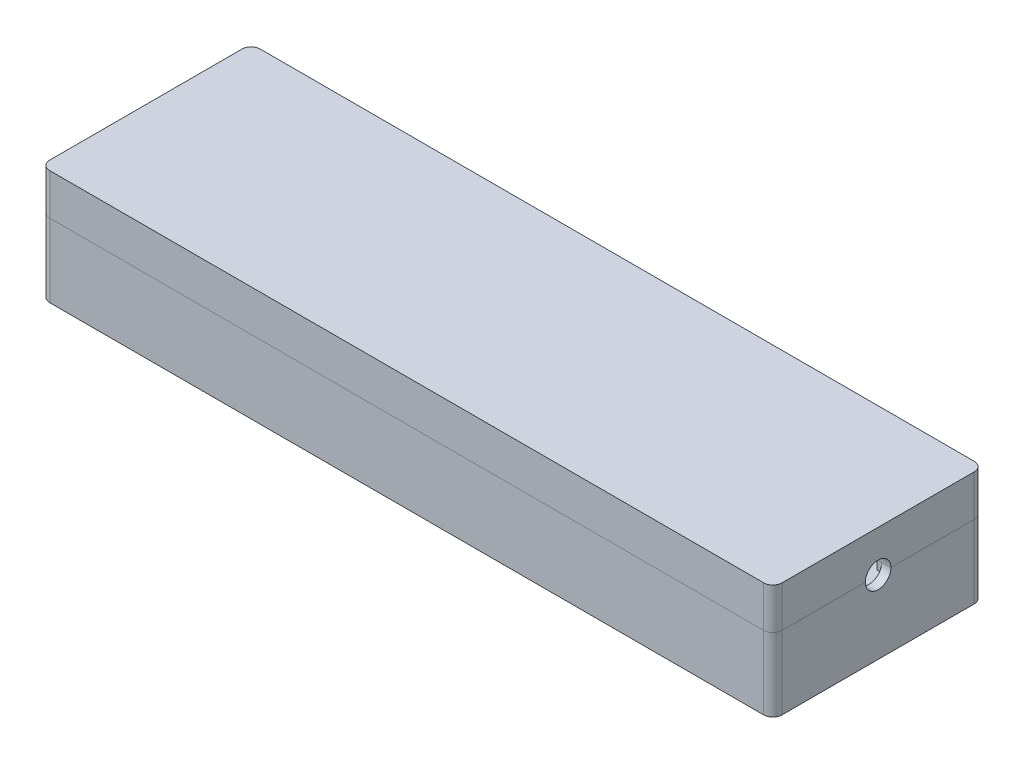
SolidWorks part; units mm, degrees
ref_plane "Front Plane" through (0, 0, 0) normal (0, 0, 1) x (1, 0, 0)
ref_plane "Top Plane" through (0, 0, 0) normal (0, 1, 0) x (1, 0, 0)
ref_plane "Right Plane" through (0, 0, 0) normal (1, 0, 0) x (0, 0, -1)
sketch "Sketch1" plane through (0, 0, 0) normal (0, 1, 0) x (1, 0, 0)
  line L0 (1, 1) -> (1, 22) construction
  line L1 (0, 0) -> (80, 0)
  line L2 (0, 0) -> (0, 23)
  line L3 (0, 23) -> (80, 23)
  line L4 (80, 0) -> (80, 23)
  line L5 (1, 22) -> (79, 22) construction
  line L6 (79, 1) -> (79, 22) construction
  line L7 (1, 1) -> (79, 1) construction
  dimension "D1" = 80
  dimension "D2" = 23
  dimension "D3" = 1
extrude "Boss-Extrude1" add sketch "Sketch1" along normal blind 8
sketch "Sketch2" plane through (0, 8, 0) normal (0, 1, 0) x (1, 0, 0)
  line L0 (1, 1) -> (1, 22) construction
  line L1 (1, 22) -> (79, 22) construction
  line L2 (1, 1) -> (79, 1) construction
  line L3 (79, 1) -> (79, 22) construction
  line L4 (1, 1) -> (1, 22)
  line L5 (1, 22) -> (79, 22)
  line L6 (1, 1) -> (79, 1)
  line L7 (79, 1) -> (79, 22)
extrude "Cut-Extrude1" cut sketch "Sketch2" against normal blind 7
sketch "Sketch3" plane through (0, 0, 0) normal (1, 0, 0) x (0, 0, -1)
  line L0 (0, 0) -> (23, 0) construction
  line L1 (0, 0) -> (23, 0) construction
  line L2 (11.5, 0) -> (11.5, 50000) construction
  line L3 (1, 8) -> (22, 8) construction
  line L4 (1, 8) -> (22, 8) construction
  line L5 (13.15, 3.65) -> (13.15, 8)
  line L6 (13.15, 8) -> (9.85, 8)
  line L7 (9.85, 8) -> (9.85, 3.65)
  arc A0 (9.85, 3.65) -> (13.15, 3.65) centre (11.5, 3.65) ccw
  arc A1 (13.15, 3.65) -> (9.85, 3.65) centre (11.5, 3.65) ccw
  arc A2 (12.7158, 4.7655) -> (13.15, 4.9345) centre (12.9, 4.9345) ccw
  arc A3 (10.2842, 4.7655) -> (9.85, 4.9345) centre (10.1, 4.9345) cw
  point P4 (11.5, 0)
  point P15 (11.5, 2)
  dimension "D1" = 3.3
  dimension "D3" = 0.5
  dimension "D2" = 2
extrude "Cut-Extrude2" cut sketch "Sketch3" along normal up to next contours A3 A1 A2 L5 L6 L7 | A2 A1 L5 | A1 A3 L7 | A0 A1 region at (0, 4.4661, -13.045) region at (0, 3.65, -11.5) region at (0, 6.5053, -11.5) region at (0, 4.4661, -9.955)
sketch "Sketch5" plane through (1, 0, 0) normal (1, 0, 0) x (0, 0, -1)
  line L0 (1, 8) -> (22, 8) construction
  line L1 (1, 8) -> (22, 8) construction
  line L2 (1, 8) -> (1, 7)
  line L3 (1, 7) -> (5, 7)
  line L4 (5, 7) -> (5, 8)
  line L5 (5, 8) -> (1, 8)
  line L6 (22, 8) -> (22, 7)
  line L7 (22, 7) -> (18, 7)
  line L8 (18, 7) -> (18, 8)
  line L9 (18, 8) -> (22, 8)
  dimension "D1" = 4
  dimension "D2" = 1
extrude "Boss-Extrude2" [suppressed] add sketch "Sketch5" along normal blind 3
chamfer "Chamfer1" [suppressed] distance 1 angle 45
fillet "Fillet1" radius 1 8 edges at (79, 4.5, -1) (79, 4.5, -22) (1, 4.5, -22) (1, 4.5, -1) (80, 4, 0) (80, 4, -23) (0, 4, -23) (0, 4, 0)
sketch "Sketch6" plane through (0, 8, 0) normal (0, 1, 0) x (1, 0, 0)
  line L0 (2, 1.5) -> (78, 1.5)
  line L1 (78.5, 2) -> (78.5, 21)
  line L2 (78, 21.5) -> (2, 21.5)
  line L3 (1.5, 21) -> (1.5, 2)
  line L4 (80, 1) -> (80, 22)
  line L5 (1, 0) -> (79, 0)
  line L6 (0, 22) -> (0, 1)
  line L7 (79, 23) -> (1, 23)
  line L8 (80, 1) -> (80, 22)
  line L9 (1, 0) -> (79, 0)
  line L10 (0, 22) -> (0, 1)
  line L11 (79, 23) -> (1, 23)
  line L12 (2, 1) -> (78, 1)
  line L13 (79, 2) -> (79, 21)
  line L14 (78, 22) -> (2, 22)
  line L15 (1, 21) -> (1, 2)
  line L16 (2, 1) -> (78, 1)
  line L17 (79, 2) -> (79, 21)
  line L18 (78, 22) -> (2, 22)
  line L19 (1, 21) -> (1, 2)
  arc A0 (78, 1.5) -> (78.5, 2) centre (78, 2) ccw
  arc A1 (78.5, 21) -> (78, 21.5) centre (78, 21) ccw
  arc A2 (2, 21.5) -> (1.5, 21) centre (2, 21) ccw
  arc A3 (1.5, 2) -> (2, 1.5) centre (2, 2) ccw
  arc A4 (79, 0) -> (80, 1) centre (79, 1) ccw
  arc A5 (0, 1) -> (1, 0) centre (1, 1) ccw
  arc A6 (1, 23) -> (0, 22) centre (1, 22) ccw
  arc A7 (80, 22) -> (79, 23) centre (79, 22) ccw
  arc A8 (79, 0) -> (80, 1) centre (79, 1) ccw
  arc A9 (0, 1) -> (1, 0) centre (1, 1) ccw
  arc A10 (1, 23) -> (0, 22) centre (1, 22) ccw
  arc A11 (80, 22) -> (79, 23) centre (79, 22) ccw
  arc A12 (78, 1) -> (79, 2) centre (78, 2) ccw
  arc A13 (79, 21) -> (78, 22) centre (78, 21) ccw
  arc A14 (2, 22) -> (1, 21) centre (2, 21) ccw
  arc A15 (1, 2) -> (2, 1) centre (2, 2) ccw
  arc A16 (78, 1) -> (79, 2) centre (78, 2) ccw
  arc A17 (79, 21) -> (78, 22) centre (78, 21) ccw
  arc A18 (2, 22) -> (1, 21) centre (2, 21) ccw
  arc A19 (1, 2) -> (2, 1) centre (2, 2) ccw
  line M9 (1, 0) -> (79, 0)
  arc M10 (79, 0) -> (80, 1) centre (79, 1) ccw
  line M11 (80, 1) -> (80, 22)
  line M13 (79, 21) -> (79, 2)
  arc M14 (79, 2) -> (78, 1) centre (78, 2) cw
  line M15 (78, 1) -> (2, 1)
  line M18 (1, 2) -> (1, 9.85)
  line M19 (1, 9.85) -> (0, 9.85)
  line M20 (0, 9.85) -> (0, 1)
  arc M21 (0, 1) -> (1, 0) centre (1, 1) ccw
  arc M22 (2, 1) -> (1, 2) centre (2, 2) cw
  arc M51 (1, 21) -> (2, 22) centre (2, 21) cw
  line M52 (2, 22) -> (78, 22)
  arc M53 (78, 22) -> (79, 21) centre (78, 21) cw
  line M61 (0, 13.15) -> (1, 13.15)
  line M62 (1, 13.15) -> (1, 21)
  dimension "D1" = 0
  dimension "D2" = 0
  dimension "D3" = 0.5
extrude "Boss-Extrude3" add sketch "Sketch6" along normal blind 4.5 separate body contours A18 L18 A17 L17 L8 A11 L11 A10 L10 L19 M19 | M21 M9 M10 M11 M13 M14 M15 M22 M18 M19 M20 | L18 A18 L19 L17 A17 M18 M22 M15 M14 M13 | L3 A3 L0 A0 L1 A1 L2 A2 | L19 L10 M61 M19 region at (40, 8, -11.5) region at (79.1185, 8, -0.8815) region at (0.5, 8, -11.5) region at (1.0808, 8, -11.5)
extrude "Cut-Extrude4" cut sketch "Sketch6<3>" along normal blind 3.5 contours L3 A3 L0 A0 L1 A1 L2 A2 region at (40, 8, -11.5)
sketch "Sketch6<3>" plane through (0, 8, 0) normal (0, 1, 0) x (1, 0, 0) same geometry as "Sketch6"
extrude "Boss-Extrude4" add sketch "Sketch6<4>" against normal blind 1 contours L19 A3 L3 A2 L2 A1 L1 A0 L0 M62 M18 M22 M15 M14 M13 M53 M52 M51 region at (1.35, 8, -1.35)
sketch "Sketch6<4>" plane through (0, 8, 0) normal (0, 1, 0) x (1, 0, 0) same geometry as "Sketch6"
sketch "Sketch4" plane through (80, 0, 0) normal (1, 0, 0) x (0, 0, -1)
  line L0 (11.5, -200000) -> (11.5, 250000) construction
  line L1 (11.5, -200000) -> (11.5, 250000)
  line L2 (11.5, -200000) -> (11.5, 250000)
  line L3 (11.5, -200000) -> (11.5, 250000)
  line L4 (0, 0) -> (23, 0) construction
  line L5 (0, 0) -> (23, 0) construction
  line L6 (1, 8) -> (22, 8) construction
  line L7 (1, 8) -> (22, 8) construction
  line L8 (11.5, 0) -> (11.5, 50000) construction
  line L9 (10.1, 8) -> (10.1, 6.6)
  line L10 (10.1, 6.6) -> (12.9, 6.6)
  line L11 (12.9, 6.6) -> (12.9, 8)
  line L12 (10.1, 8) -> (12.9, 8)
  circle A0 centre (11.5, 8) radius 1.4
  point P10 (11.5, 0)
  dimension "D1" = 2.8
extrude "Cut-Extrude3" cut sketch "Sketch4" against normal up to surface (1.5 mm away) contours A0 up to face at (78.5, 9.25, -11.5)
extrude "Boss-Extrude5" add sketch "Sketch3<3>" along normal up to surface (1.5 mm away) contours A3 A1 A2 L5 L6 L7 region at (0, 6.5053, -11.5) up to face at (1.5, 9.25, -11.5)
sketch "Sketch3<3>" plane through (0, 0, 0) normal (1, 0, 0) x (0, 0, -1) same geometry as "Sketch3"
extrude "Cut-Extrude19" cut sketch "Sketch4<3>" against normal up to surface (1.5 mm away) contours L10 L11 L12 L9 up to face at (78.5, 8.9, -11.5)
sketch "Sketch4<3>" plane through (80, 0, 0) normal (1, 0, 0) x (0, 0, -1) same geometry as "Sketch4"
chamfer "Chamfer2" distance 1 angle 45 2 edges at (0.5, 8, -9.85) (0.5, 8, -13.15)
chamfer "Chamfer3" distance 1 angle 45 2 edges at (0.5, 8, -9.85) (0.5, 8, -13.15)
sketch "Sketch7" plane through (0, 1, 0) normal (0, 1, 0) x (1, 0, 0)
  line L0 (78, 22) -> (2, 22) construction
  line L1 (2, 1) -> (78, 1) construction
  line L2 (58.928, 22) -> (57.928, 22)
  line L3 (57.928, 1) -> (58.928, 1)
  line L4 (57.928, 22) -> (57.928, 1)
  line L5 (58.928, 22) -> (58.928, 1)
  dimension "D1" = 58.928
  dimension "D2" = 1
extrude "Boss-Extrude6" add sketch "Sketch7" along normal blind 10.5
sketch "Sketch8" plane through (57.928, 0, 0) normal (-1, 0, 0) x (0, 0, 1)
  line L0 (-22, 11.5) -> (-1, 11.5) construction
  line L1 (-22, 11.5) -> (-1, 11.5) construction
  line L2 (-11.5, 11.6181) -> (-11.5, 14.876) construction
  line L3 (-16, 4.75) -> (-7, 4.75)
  line L4 (-22, 1) -> (-1, 1) construction
  line L5 (-22, 1) -> (-1, 1) construction
  line L6 (-16.5, 5.25) -> (-16.5, 11)
  line L7 (-18.2274, 11.5) -> (-17, 11.5)
  line L8 (-18.6477, 11.2709) -> (-21.4, 7)
  line L9 (-21.4, 7) -> (-22, 7)
  line L10 (-22, 7) -> (-22, 11.5)
  line L11 (-12.9, 8) -> (-21, 8) construction
  line L12 (-12.9, 8) -> (-21, 8) construction
  line L13 (-22, 11.5) -> (-22, 13.5278)
  line L14 (-22, 13.5278) -> (-1, 13.5278)
  line L15 (-1, 13.5278) -> (-1, 7)
  line L16 (-1, 7) -> (-1.6, 7)
  line L17 (-1.6, 7) -> (-4.3523, 11.2709)
  line L18 (-4.7726, 11.5) -> (-6, 11.5)
  line L19 (-6.5, 11) -> (-6.5, 5.25)
  arc A0 (-7, 4.75) -> (-6.5, 5.25) centre (-7, 5.25) ccw
  arc A1 (-16, 4.75) -> (-16.5, 5.25) centre (-16, 5.25) cw
  arc A2 (-4.3523, 11.2709) -> (-4.7726, 11.5) centre (-4.7726, 11) ccw
  arc A3 (-6, 11.5) -> (-6.5, 11) centre (-6, 11) ccw
  arc A4 (-16.5, 11) -> (-17, 11.5) centre (-17, 11) ccw
  arc A5 (-18.2274, 11.5) -> (-18.6477, 11.2709) centre (-18.2274, 11) ccw
  point P6 (-11.5, 4.75)
  point P11 (-11.5, 11.5)
  point P28 (-6.5, 4.75)
  point P31 (-16.5, 4.75)
  point P34 (-4.5, 11.5)
  point P37 (-6.5, 11.5)
  point P40 (-16.5, 11.5)
  point P43 (-18.5, 11.5)
  dimension "D6" = 0.5
  dimension "D1" = 3.75
  dimension "D2" = 10
  dimension "D3" = 2
  dimension "D4" = 1
  dimension "D5" = 0.6
extrude "Cut-Extrude20" cut sketch "Sketch8" against normal up to next (1 mm away)
fillet "Fillet2" radius 0.5 4 edges at (58.928, 4, -1) (57.928, 4, -1) (58.928, 4, -22) (57.928, 4, -22)
